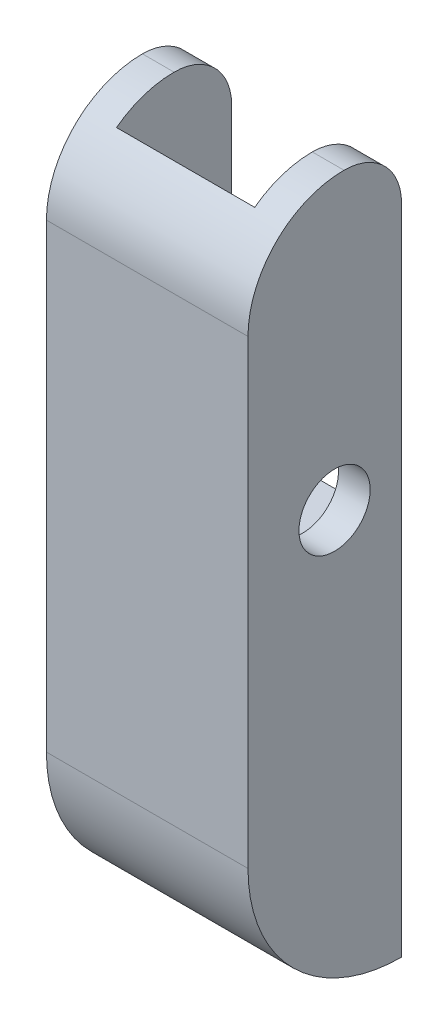
SolidWorks part; units mm, degrees
ref_plane "Front Plane" through (0, 0, 0) normal (0, 0, 1) x (1, 0, 0)
ref_plane "Top Plane" through (0, 0, 0) normal (0, 1, 0) x (1, 0, 0)
ref_plane "Right Plane" through (0, 0, 0) normal (1, 0, 0) x (0, 0, -1)
sketch "Sketch1" plane through (0, 0, 0) normal (0, 0, 1) x (1, 0, 0)
  line L1 (0, 0) -> (13.335, 0)
  line L2 (0, 0) -> (0, 46.99)
  line L3 (0, 46.99) -> (13.335, 46.99)
  line L4 (13.335, 0) -> (13.335, 46.99)
  dimension "D1" = 13.335
  dimension "D2" = 46.99
extrude "Boss-Extrude1" add sketch "Sketch1" along normal blind 10.16 contours L2 L3 L4 L1
fillet "Fillet5" radius 3.81 1 edges at (6.6675, 46.99, 0)
sketch "Sketch2" plane through (0, 0, 0) normal (0, 0, -1) x (-1, 0, 0)
  line L0 (0, 46.99) -> (-13.335, 46.99) construction
  line L1 (-11.2395, 46.99) -> (-2.0955, 46.99)
  line L2 (-11.2395, 46.99) -> (-11.2395, 24.638)
  line L3 (-11.2395, 24.638) -> (-2.0955, 24.638)
  line L4 (-2.0955, 46.99) -> (-2.0955, 24.638)
  line L5 (0, 0) -> (0, 43.18) construction
  dimension "D1" = 22.352
  dimension "D2" = 9.144
  dimension "D3" = 2.0955
extrude "Cut-Extrude1" cut sketch "Sketch2" against normal blind 7.62
sketch "Sketch3" plane through (0, 0, 0) normal (-1, 0, 0) x (0, 0, 1)
  line L0 (7.62, 46.99) -> (7.62, 24.638) construction
  line L2 (7.62, 24.638) -> (0, 24.638) construction
  circle A0 centre (4.4323, 27.8257) radius 2.3558
  point P6 (-37.2931, 27.6052)
  dimension "D1" = 3.1877
  dimension "D3" = 4.7117
  dimension "D2" = 3.1877
extrude "Cut-Extrude2" cut sketch "Sketch3" against normal through all and the other way through all
fillet "Fillet4" radius 6.35 1 edges at (6.6675, 46.99, 10.16)
fillet "Fillet6" radius 10.16 1 edges at (6.6675, 0, 10.16)
